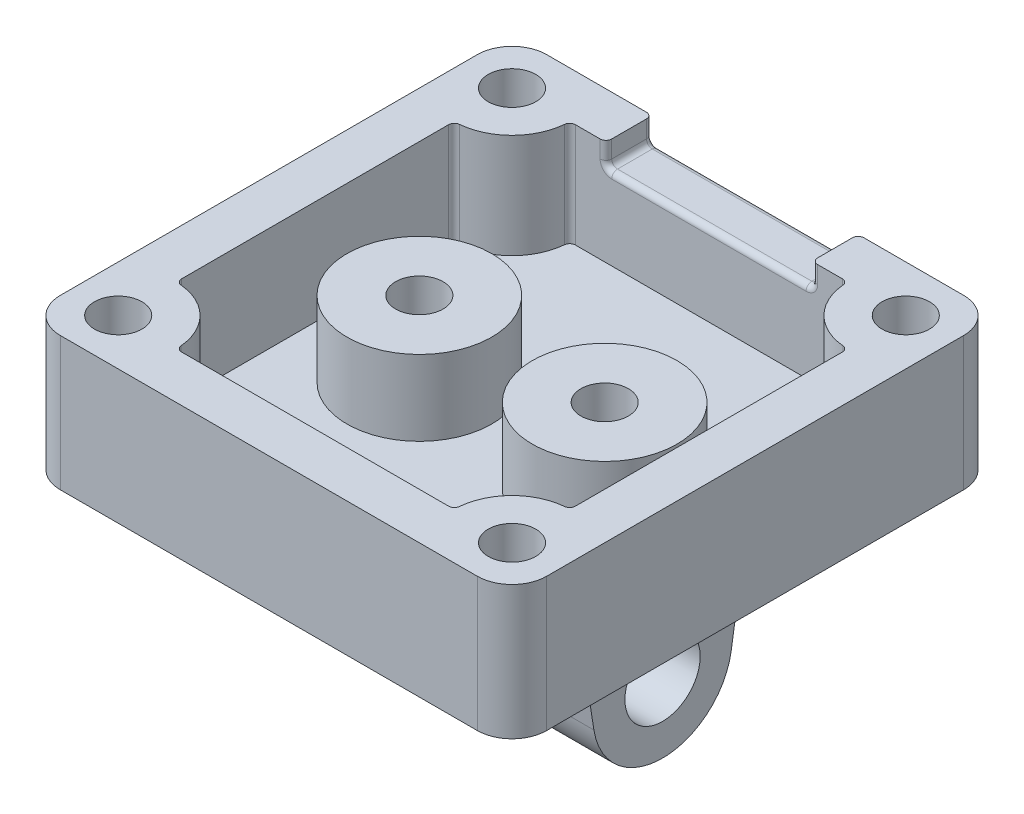
SolidWorks part; units mm, degrees
material "ABS"
ref_plane "Front Plane" through (0, 0, 0) normal (0, 0, 1) x (1, 0, 0)
ref_plane "Top Plane" through (0, 0, 0) normal (0, 1, 0) x (1, 0, 0)
ref_plane "Right Plane" through (0, 0, 0) normal (1, 0, 0) x (0, 0, -1)
sketch "Sketch1" plane through (0, 0, 0) normal (0, 1, 0) x (1, 0, 0)
  line L1 (-21, 21) -> (21, 21)
  line L2 (-21, 21) -> (-21, -21)
  line L3 (-21, -21) -> (21, -21)
  line L4 (21, 21) -> (21, -21)
  line L5 (-21, 21) -> (21, -21) construction
  line L6 (-21, -21) -> (21, 21) construction
  point P0 (0, 0)
  dimension "D1" = 42
  dimension "D2" = 42
extrude "Boss-Extrude1" add sketch "Sketch1" along normal blind 2.54
sketch "Sketch2" plane through (0, 2.54, 0) normal (0, 1, 0) x (1, 0, 0)
  line L26 (-21, 21) -> (21, 21)
  line L44 (-21, 21) -> (-21, -21)
  line L45 (-21, -21) -> (21, -21)
  line L49 (21, 21) -> (21, -21)
  line L50 (-21, 21) -> (21, -21) construction
  line L51 (-21, -21) -> (21, 21) construction
  line L55 (-17, 11.5228) -> (-17, -11.5228)
  line L56 (-11.5228, -17) -> (11.5228, -17)
  line L57 (17, 11.5228) -> (17, -11.5228)
  line L58 (-11.5228, 17) -> (11.5228, 17)
  line L63 (-17, 17) -> (-17, -17) construction
  line L64 (-17, -17) -> (17, -17) construction
  line L65 (17, 17) -> (17, -17) construction
  line L66 (-17, 17) -> (17, 17) construction
  line L68 (-13.4645, 13.4645) -> (13.4645, 13.4645) construction
  line L69 (-13.4645, 13.4645) -> (-13.4645, -13.4645) construction
  line L70 (-13.4645, -13.4645) -> (13.4645, -13.4645) construction
  line L71 (13.4645, 13.4645) -> (13.4645, -13.4645) construction
  line L72 (-13.4645, 13.4645) -> (13.4645, -13.4645) construction
  line L73 (-13.4645, -13.4645) -> (13.4645, 13.4645) construction
  arc A0 (-16.5455, -12.0207) -> (-12.0207, -16.5455) centre (-17, -17) cw
  arc A2 (12.0207, -16.5455) -> (16.5455, -12.0207) centre (17, -17) cw
  arc A4 (16.5455, 12.0207) -> (12.0207, 16.5455) centre (17, 17) cw
  arc A6 (-12.0207, 16.5455) -> (-16.5455, 12.0207) centre (-17, 17) cw
  arc A8 (-16.5455, -12.0207) -> (-17, -11.5228) centre (-16.5, -11.5228) cw
  arc A9 (-12.0207, -16.5455) -> (-11.5228, -17) centre (-11.5228, -16.5) ccw
  arc A10 (12.0207, -16.5455) -> (11.5228, -17) centre (11.5228, -16.5) cw
  arc A11 (16.5455, -12.0207) -> (17, -11.5228) centre (16.5, -11.5228) ccw
  arc A12 (16.5455, 12.0207) -> (17, 11.5228) centre (16.5, 11.5228) cw
  arc A13 (12.0207, 16.5455) -> (11.5228, 17) centre (11.5228, 16.5) ccw
  arc A14 (-12.0207, 16.5455) -> (-11.5228, 17) centre (-11.5228, 16.5) cw
  arc A15 (-16.5455, 12.0207) -> (-17, 11.5228) centre (-16.5, 11.5228) ccw
  point P0 (0, 0)
  point P44 (0, 0)
  dimension "D2" = 5
  dimension "D3" = 0.5
  dimension "D1" = 4
  dimension "D4" = 26.9289
  dimension "D5" = 26.9289
extrude "Boss-Extrude2" add sketch "Sketch2" along normal blind 9
ref_plane "Plane1" through (0, 0, 0) normal (1, 0, 0) x (0, 0, -1)
sketch "Sketch4" plane through (-21, 0, 0) normal (-1, 0, 0) x (0, 0, 1)
  line L0 (7.5, 0) -> (5.9271, -10)
  line L1 (-21, 0) -> (21, 0) construction
  line L2 (-5.9271, -10) -> (-7.5, 0)
  line L3 (7.5, 0) -> (-7.5, 0)
  arc A0 (5.9271, -10) -> (-5.9271, -10) centre (0, -9.0677) cw
  circle A1 centre (0, -9.0677) radius 3.25
  point P11 (0, 0)
  point P12 (0, 0)
  dimension "D1" = 6.5
  dimension "D4" = 6
  dimension "D2" = 10
  dimension "D3" = 15
extrude "Boss-Extrude4" [suppressed] add sketch "Sketch4" against normal up to surface (42 mm away) up to face at (21, 5.77, 0)
mirror "Mirror1" [suppressed] about plane through (0, 0, 0) normal (1, 0, 0)
sketch "Sketch13" plane through (0, 0, 0) normal (1, 0, 0) x (0, 0, -1)
  line L3 (-7.5, 0) -> (-5.9271, -10)
  line L4 (5.9271, -10) -> (7.5, 0)
  line L5 (7.5, 0) -> (-7.5, 0)
  line L6 (-7.5, 0) -> (-5.9271, -10)
  line L7 (5.9271, -10) -> (7.5, 0)
  line L8 (7.5, 0) -> (-7.5, 0)
  circle A1 centre (0, -9.0677) radius 3.25
  circle A2 centre (0, -9.0677) radius 3.25
  arc A3 (-5.9271, -10) -> (5.9271, -10) centre (0, -9.0677) ccw
  arc A4 (-5.9271, -10) -> (5.9271, -10) centre (0, -9.0677) ccw
  dimension "D1" = 0
  dimension "D2" = 0
extrude "Boss-Extrude6" add sketch "Sketch13" along normal mid plane 26
sketch "Sketch9" plane through (0, 2.54, 0) normal (0, 1, 0) x (1, 0, 0)
  line L0 (0, -55) -> (0, 55) construction
  line L1 (0, 0) -> (-8, 0) construction
  circle A0 centre (8, 0) radius 2.05
  circle A1 centre (8, 0) radius 6.25
  circle A2 centre (-8, 0) radius 6.25
  circle A3 centre (-8, 0) radius 2.05
  dimension "D1" = 4.1
  dimension "D2" = 4.2
  dimension "D3" = 8
extrude "Boss-Extrude5" add sketch "Sketch9" along normal blind 6.5
sketch "Sketch10" plane through (0, 11.54, 0) normal (0, 1, 0) x (1, 0, 0)
  circle A0 centre (-17, 17) radius 2.05
  circle A1 centre (17, 17) radius 2.05
  circle A2 centre (-17, -17) radius 2.05
  circle A3 centre (17, -17) radius 2.05
  dimension "D1" = 4.1
extrude "Cut-Extrude1" cut sketch "Sketch10" against normal blind 8
sketch "Sketch12" plane through (0, 0, -21) normal (0, 0, -1) x (-1, 0, 0)
  line L0 (-21, 11.54) -> (21, 11.54) construction
  line L1 (8.89, 9.54) -> (-8.89, 9.54)
  line L2 (8.89, 9.54) -> (8.89, 11.54)
  line L3 (8.89, 11.54) -> (-8.89, 11.54)
  line L4 (-8.89, 9.54) -> (-8.89, 11.54)
  line L5 (8.89, 9.54) -> (-8.89, 11.54) construction
  line L6 (8.89, 11.54) -> (-8.89, 9.54) construction
  point P0 (0, 10.54)
  point P7 (0, 11.54)
  point P8 (0, 11.54)
  dimension "D1" = 2
  dimension "D2" = 17.78
extrude "Cut-Extrude2" cut sketch "Sketch12" against normal up to surface (4 mm away) up to face at (0, 7.04, -17)
fillet "Fillet1" radius 3 4 edges at (21, 5.77, 21) (-21, 5.77, 21) (-21, 5.77, -21) (21, 5.77, -21)
fillet "Fillet2" radius 0.5 8 edges at (-8.89, 10.54, -21) (8.89, 10.54, -21) (0, 9.54, -21) (0, 9.54, -17) (-8.89, 10.54, -17) (8.89, 10.54, -17) (8.89, 9.54, -19) (-8.89, 9.54, -19)
fillet "Fillet3" radius 3 2 edges at (0, 0, -7.5) (0, 0, 7.5)
